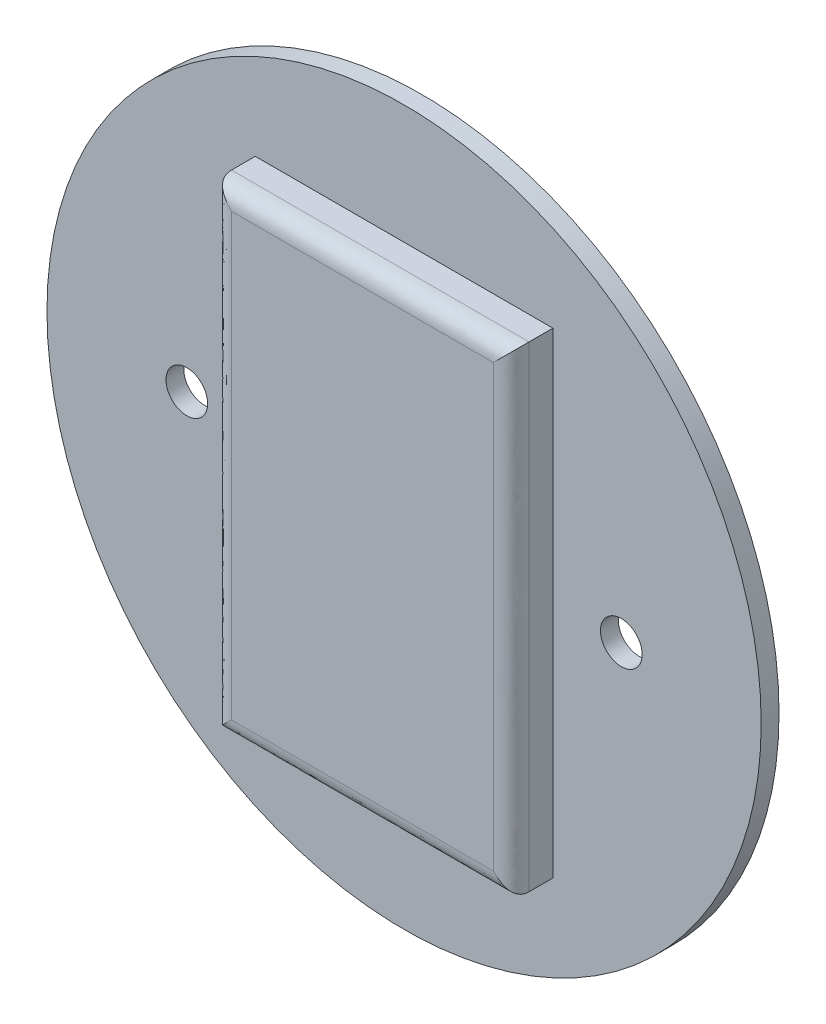
SolidWorks part; units mm, degrees
note: The reader was unsure of these and kept them because the rebuilt part matched: shared geometry of "草图1<9>", "草图1<10>", "草图1<11>".
ref_plane "前视基准面" through (0, 0, 0) normal (0, 0, 1) x (1, 0, 0)
ref_plane "上视基准面" through (0, 0, 0) normal (0, 1, 0) x (1, 0, 0)
ref_plane "右视基准面" through (0, 0, 0) normal (1, 0, 0) x (0, 0, -1)
sketch "草图1" plane through (0, 0, 0) normal (0, 0, 1) x (1, 0, 0)
  line L0 (0, 0) -> (0, -30) construction
  line L1 (-12.5, -20) -> (12.5, -20)
  line L2 (-12.5, -20) -> (-12.5, 20)
  line L3 (-12.5, 20) -> (12.5, 20)
  line L4 (12.5, -20) -> (12.5, 20)
  line L5 (-12.5, -20) -> (12.5, 20) construction
  line L6 (-12.5, 20) -> (12.5, -20) construction
  line L7 (0, 0) -> (18.25, 0)
  line L8 (-3.5, -28) -> (3.5, -28)
  line L9 (-3.5, -28) -> (-3.5, -21)
  line L10 (-3.5, -21) -> (3.5, -21)
  line L11 (3.5, -28) -> (3.5, -21)
  line L12 (-3.5, -28) -> (3.5, -21) construction
  line L13 (-3.5, -21) -> (3.5, -28) construction
  line L14 (-3.5, -24.5) -> (-6, -24.5) construction
  line L15 (0, 0) -> (-18.25, 0)
  circle A0 centre (0, 0) radius 30
  circle A2 centre (8, -24.5) radius 2
  circle A3 centre (-8, -24.5) radius 2
  circle A4 centre (18.25, 0) radius 1.75
  circle A5 centre (-18.25, 0) radius 1.75
  point P7 (0, -24.5)
  dimension "D1" = 25
  dimension "D3" = 60
  dimension "D7" = 8
  dimension "D10" = 4
  dimension "D11" = 4
  dimension "D15" = 3.5
  dimension "D16" = 3.5
  dimension "D2" = 40
  dimension "D4" = 7
  dimension "D5" = 7
  dimension "D6" = 4.5
  dimension "D8" = 8
  dimension "D9" = 8
  dimension "D12" = 2.5
  dimension "D13" = 18.25
  dimension "D14" = 18.25
extrude "凸台-拉伸6" add sketch "草图1" along normal blind 1.5 contours A0 A3 A2 L4 L1 L2 L3 L11 L8 L9 L10 | A3 | L8 L11 L10 L9 | A2
extrude "凸台-拉伸7" add sketch "草图1<9>" along normal blind 5 contours L1 L4 L3 L2
sketch "草图1<9>" plane through (0, 0, 0) normal (0, 0, 1) x (1, 0, 0) same geometry as "草图1"
extrude "凸台-拉伸8" add sketch "草图1<10>" against normal blind 6 contours A2 | L8 L11 L10 L9 | A3
sketch "草图1<10>" plane through (0, 0, 0) normal (0, 0, 1) x (1, 0, 0) same geometry as "草图1"
fillet "圆角3" radius 1.5 1 edges at (10, -24.5, -6)
fillet "圆角4" radius 1.5 1 edges at (-6, -24.5, -6)
extrude "凸台-拉伸9" add sketch "草图1<11>" along normal blind 5 contours L7 L15 L2 L1 L4
sketch "草图1<11>" plane through (0, 0, 0) normal (0, 0, 1) x (1, 0, 0) same geometry as "草图1"
fillet "圆角5" radius 1.5 4 edges at (0, 20, 5) (12.5, 0, 5) (0, -20, 5) (-12.5, 0, 5)
